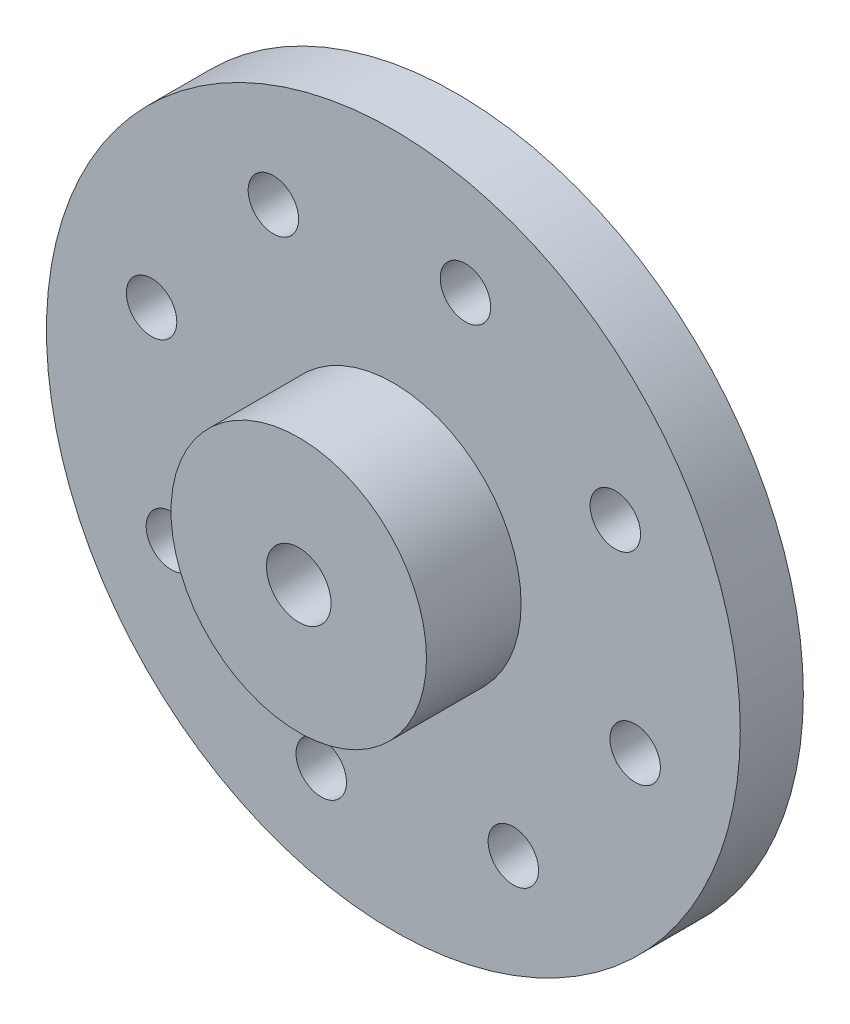
SolidWorks part; units mm, degrees
ref_plane "Front Plane" through (0, 0, 0) normal (0, 0, 1) x (1, 0, 0)
ref_plane "Top Plane" through (0, 0, 0) normal (0, 1, 0) x (1, 0, 0)
ref_plane "Right Plane" through (0, 0, 0) normal (1, 0, 0) x (0, 0, -1)
sketch "Sketch1" plane through (0, 0, 0) normal (0, 0, 1) x (1, 0, 0)
  circle A0 centre (0, 0) radius 11
  circle A1 centre (0, 0) radius 2.6699
  point P24 (0, 0)
  dimension "D1" = 22
  dimension "D2" = 5.3397
extrude "Boss-Extrude1" add sketch "Sketch1" along normal blind 2
sketch "Sketch2" plane through (0, 0, 2) normal (0, 0, 1) x (1, 0, 0)
  circle A1 centre (0, 0) radius 4.05
  dimension "D1" = 8.1
extrude "Boss-Extrude2" add sketch "Sketch2" along normal blind 3
sketch "Sketch3" plane through (0, 0, 0) normal (0, 0, -1) x (-1, 0, 0)
  circle A0 centre (0, 0) radius 2.6699
  circle A1 centre (0, 0) radius 4
extrude "Boss-Extrude3" add sketch "Sketch3" along normal blind 1
chamfer "Chamfer1" distance 0.6 angle 45 1 edges at (-4, 0, -1)
hole_wizard "M2 Tapped Hole1" positions "Sketch4" profile "Sketch5" tap size "M2" standard "ISO" end condition through all
sketch "Sketch4" plane through (0, 0, 2) normal (0, 0, 1) x (1, 0, 0)
  point P0 (2.2862, 7.6664)
  point P9 (7.0375, 3.8044)
  point P10 (7.6664, -2.2862)
  point P11 (3.8044, -7.0375)
  point P12 (-2.2862, -7.6664)
  point P13 (-7.0375, -3.8044)
  point P14 (-7.6664, 2.2862)
  point P15 (-3.8044, 7.0375)
  point P16 (0, 0)
  dimension "D1" = 8
  dimension "D2" = 8
sketch "Sketch5" plane through (2.2862, 7.6664, 2) normal (1, 0, 0) x (0, -1, 0)
  line L0 (0, 0) -> (0, 3)
  line L1 (0, 3) -> (0.8, 3)
  line L2 (0.8, 3) -> (0.8, 0)
  line L5 (0.8, 0) -> (0, 0)
  line L11 (0, -6.35) -> (0, 107.95) construction
  dimension "Thru Tap Drill Dia." = 1.6
  dimension "Thru Tap Drill Depth" = 3
cosmetic thread "Hole Thread1" parameters "D2"=2
cosmetic thread "Hole Thread2" parameters "D2"=2
cosmetic thread "Hole Thread3" parameters "D2"=2
cosmetic thread "Hole Thread4" parameters "D2"=2
cosmetic thread "Hole Thread5" parameters "D2"=2
cosmetic thread "Hole Thread6" parameters "D2"=2
cosmetic thread "Hole Thread7" parameters "D2"=2
cosmetic thread "Hole Thread8" parameters "D2"=2
hole_wizard "M2.5 Tapped Hole1" positions "Sketch6" profile "Sketch7" tap size "M2.5" standard "ISO"
sketch "Sketch6" plane through (0, 0, 5) normal (0, 0, 1) x (1, 0, 0)
  point P0 (0, 0)
sketch "Sketch7" plane through (0, 0, 5) normal (1, 0, 0) x (0, -1, 0)
  line L0 (0, 0) -> (0, 6.9659)
  line L1 (0, 6.9659) -> (1.025, 6.35)
  line L2 (1.025, 6.35) -> (1.025, 0)
  line L5 (1.025, 0) -> (0, 0)
  line L10 (0, 6.9659) -> (-1.025, 6.35) construction
  line L11 (0, -6.35) -> (0, 107.95) construction
  dimension "Tap Drill Dia." = 2.05
  dimension "Tap Drill Depth" = 6.35
  dimension "Drill Angle" = 118
cosmetic thread "Hole Thread9" parameters "D1"=3, "D2"=2.5
